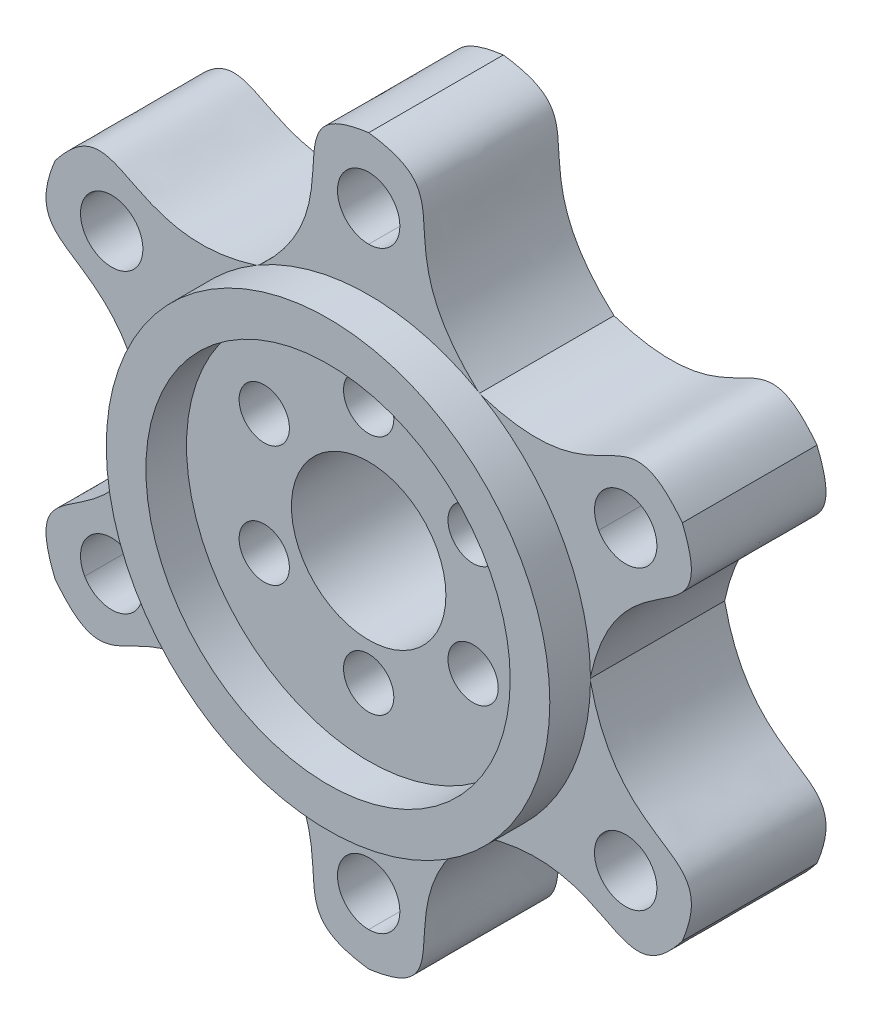
SolidWorks part; units mm, degrees
ref_plane "Front Plane" through (0, 0, 0) normal (0, 0, 1) x (1, 0, 0)
ref_plane "Top Plane" through (0, 0, 0) normal (0, 1, 0) x (1, 0, 0)
ref_plane "Right Plane" through (0, 0, 0) normal (1, 0, 0) x (0, 0, -1)
sketch "Sketch1" plane through (0, 0, 0) normal (0, 0, 1) x (1, 0, 0)
  line L0 (0, -55) -> (0, 55) construction
  line L1 (0, 0) -> (0, 45.72) construction
  circle A0 centre (0, 0) radius 9.75
  circle A1 centre (0, 0) radius 45.72
  circle A2 centre (0, 16.002) radius 3.175
  circle A3 centre (13.1849, 8.3897) radius 3.175
  circle A4 centre (13.1849, -6.8349) radius 3.175
  circle A5 centre (0, -14.4471) radius 3.175
  circle A6 centre (-13.1849, -6.8349) radius 3.175
  circle A7 centre (-13.1849, 8.3897) radius 3.175
  circle A8 centre (0, 37.465) radius 3.937
  circle A10 centre (32.4456, 18.7325) radius 3.937
  circle A11 centre (32.4456, -18.7325) radius 3.937
  circle A12 centre (0, -37.465) radius 3.937
  circle A13 centre (-32.4456, -18.7325) radius 3.937
  circle A14 centre (-32.4456, 18.7325) radius 3.937
  point P21 (0, 0.7774)
  point P36 (0, 0)
  dimension "D1" = 19.5
  dimension "D2" = 91.44
  dimension "D3" = 6.35
  dimension "D6" = 7.874
  dimension "D4" = 16.002
  dimension "D8" = 37.465
  dimension "D5" = 6
  dimension "D7" = 6
extrude "Boss-Extrude3" add sketch "Sketch1" along normal blind 17
sketch "Sketch2" plane through (0, 0, 17) normal (0, 0, 1) x (1, 0, 0)
  line L0 (0, -55) -> (0, 55) construction
  line L1 (-32.4456, 18.7325) -> (0, 37.465) construction
  line L2 (-16.2228, 28.0988) -> (-4.875, 8.4437) construction
  line L3 (16.1678, 28.1305) -> (4.8199, 8.4753) construction
  line L6 (32.4456, -18.7325) -> (32.4456, 18.7325) construction
  line L7 (32.4456, 18.7325) -> (0, 37.465) construction
  line L8 (55, 0) -> (-55, 0) construction
  circle A0 centre (0, 0) radius 27.94 construction
  circle A1 centre (0, 0) radius 45.72 construction
  circle A2 centre (0, 0) radius 9.75 construction
  circle A3 centre (0, 0) radius 45.72
  spline S0 degree 3 poles (-13.97, 24.1967) (-0.9195, 35.9832) (-13.1193, 43.9586) (0, 45.72) knots 0 0 0 0 1 1 1 1
  spline S1 degree 3 poles (13.97, 24.1967) (0.9195, 35.9832) (13.1193, 43.9586) (0, 45.72) knots 0 0 0 0 1 1 1 1
  spline S2 degree 3 poles (-27.94, 0) (-31.6221, 17.1953) (-44.6289, 10.6177) (-39.5947, 22.86) knots 0 0 0 0 1 1 1 1
  spline S3 degree 3 poles (-13.97, 24.1967) (-30.7026, 18.7879) (-31.5096, 33.3409) (-39.5947, 22.86) knots 0 0 0 0 1 1 1 1
  spline S4 degree 3 poles (-13.97, -24.1967) (-30.7026, -18.7879) (-31.5096, -33.3409) (-39.5947, -22.86) knots 0 0 0 0 1 1 1 1
  spline S5 degree 3 poles (-27.94, 0) (-31.6221, -17.1953) (-44.6289, -10.6177) (-39.5947, -22.86) knots 0 0 0 0 1 1 1 1
  spline S6 degree 3 poles (13.97, -24.1967) (30.7026, -18.7879) (31.5096, -33.3409) (39.5947, -22.86) knots 0 0 0 0 1 1 1 1
  spline S7 degree 3 poles (27.94, 0) (31.6221, -17.1953) (44.6289, -10.6177) (39.5947, -22.86) knots 0 0 0 0 1 1 1 1
  spline S8 degree 3 poles (13.97, -24.1967) (0.9195, -35.9832) (13.1193, -43.9586) (0, -45.72) knots 0 0 0 0 1 1 1 1
  spline S9 degree 3 poles (-13.97, -24.1967) (-0.9195, -35.9832) (-13.1193, -43.9586) (0, -45.72) knots 0 0 0 0 1 1 1 1
  spline S10 degree 3 poles (27.94, 0) (31.6221, 17.1953) (44.6289, 10.6177) (39.5947, 22.86) knots 0 0 0 0 1 1 1 1
  spline S11 degree 3 poles (13.97, 24.1967) (30.7026, 18.7879) (31.5096, 33.3409) (39.5947, 22.86) knots 0 0 0 0 1 1 1 1
  point P5 (-16.2228, 28.0988)
  point P6 (16.1678, 28.1305)
  circle M8 centre (0, 0) radius 45.72
  dimension "D1" = 55.88
  dimension "D2" = 18.796
extrude "Cut-Extrude1" cut sketch "Sketch2" against normal blind 22.86 contours S1 S11 M8 | S5 S2 A3 | S10 S7 A3 | S6 S8 A3 | S9 S4 M8 | S3 S0 M8 region at (38.1245, 0, 17) region at (19.0622, 33.0168, 17) region at (19.0622, -33.0168, 17) region at (-19.0622, 33.0168, 17) region at (-19.0622, -33.0168, 17) region at (-38.1245, 0, 17)
sketch "Sketch4" plane through (0, 0, 17) normal (0, 0, 1) x (1, 0, 0)
  circle A0 centre (0, 0) radius 9.75 construction
  circle A1 centre (0, 0) radius 9.75 construction
  circle A2 centre (0, 0) radius 28
  circle A3 centre (0, 0) radius 23
  dimension "D1" = 56
  dimension "D2" = 46
extrude "Boss-Extrude4" add sketch "Sketch4" along normal blind 5.1308 contours A2 | A3
ref_plane "Plane1" through (0, 0, 0) normal (1, 0, 0) x (0, 0, -1)
ref_plane "Plane2" through (0, 0, 0) normal (-0.5, -0.866, 0) x (-0.866, 0.5, 0)
ref_plane "Plane3" through (0, 0, 0) normal (-0.5, 0.866, 0) x (0.866, 0.5, 0)
split line "Split Line1"
split line "Split Line2"
split line "Split Line3"
ref_axis "Axis1" through (0, 0, 17) along (0, 0, -1)
